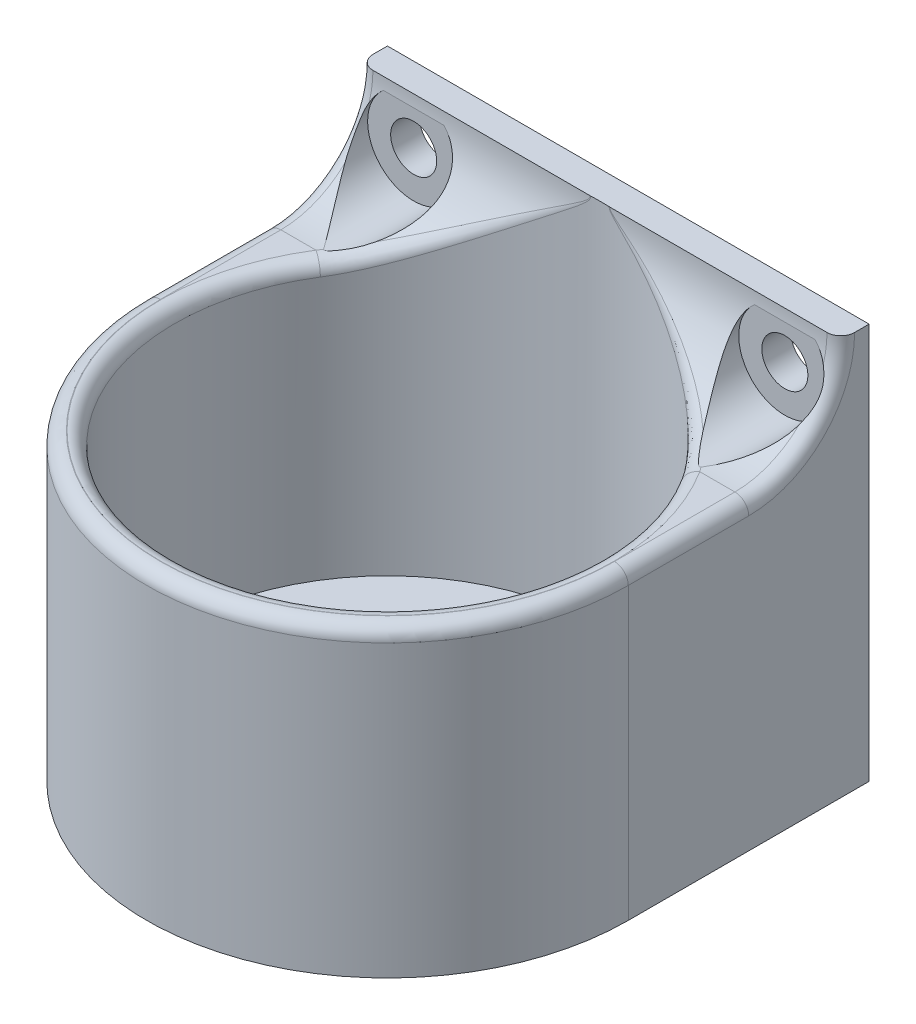
SolidWorks part; units mm, degrees
ref_plane "Front Plane" through (0, 0, 0) normal (0, 0, 1) x (1, 0, 0)
ref_plane "Top Plane" through (0, 0, 0) normal (0, 1, 0) x (1, 0, 0)
ref_plane "Right Plane" through (0, 0, 0) normal (1, 0, 0) x (0, 0, -1)
sketch "Sketch1" plane through (0, 0, 0) normal (0, 1, 0) x (1, 0, 0)
  circle A0 centre (0, 0) radius 26.15
  dimension "D1" = 52.3
extrude "Boss-Extrude1" add sketch "Sketch1" along normal blind 43
sketch "Sketch2" plane through (0, 43, 0) normal (0, 1, 0) x (1, 0, 0)
  line L0 (-26.15, 0) -> (-26.15, 26.15)
  line L1 (-26.15, 26.15) -> (0, 26.15)
  line L2 (0, 26.15) -> (26.15, 26.15)
  line L3 (26.15, 26.15) -> (26.15, 0)
  line L4 (26.15, 0) -> (-26.15, 0)
  circle A0 centre (0, 0) radius 26.15 construction
extrude "Boss-Extrude2" add sketch "Sketch2" against normal up to surface (43 mm away) up to face at (0, 0, 26.15)
sketch "Sketch3" plane through (0, 43, 0) normal (0, 1, 0) x (1, 0, 0)
  circle A0 centre (0, 0) radius 23.1
  dimension "D1" = 46.2
extrude "Cut-Extrude1" cut sketch "Sketch3" against normal offset from surface (40 mm away) 3 up to face at (0, 0, -6.5375)
sketch "Sketch5" plane through (0, 43, 0) normal (0, 1, 0) x (1, 0, 0)
  line L1 (-32.5077, 23.0771) -> (34.5641, 23.0771)
  line L2 (-32.5077, 23.0771) -> (-32.5077, -29.009)
  line L3 (-32.5077, -29.009) -> (34.5641, -29.009)
  line L4 (34.5641, 23.0771) -> (34.5641, -29.009)
  circle A0 centre (0, 0) radius 23.1 construction
  point P4 (1.0282, 23.0771)
extrude "Cut-Extrude3" cut sketch "Sketch5" against normal blind 10
sketch "Sketch6" plane through (0, 0, 0) normal (0, -1, 0) x (1, 0, 0)
  circle A0 centre (0, 0) radius 10
  dimension "D1" = 20
extrude "Cut-Extrude4" cut sketch "Sketch6" against normal up to surface (3 mm away) up to face at (0, 3, 23.1)
sketch "Sketch7" plane through (0, 0, -26.15) normal (0, 0, -1) x (-1, 0, 0)
  line L0 (-26.15, 0) -> (-26.15, 43) construction
  line L1 (26.15, 0) -> (26.15, 43) construction
  line L2 (-26.15, 43) -> (26.15, 43) construction
  circle A0 centre (-20.15, 38) radius 2.5
  circle A1 centre (20.15, 38) radius 2.5
  point P4 (0, 0)
  dimension "D1" = 5
  dimension "D2" = 5
  dimension "D3" = 6
  dimension "D4" = 6
  dimension "D5" = 5
extrude "Cut-Extrude5" cut sketch "Sketch7" against normal through all
fillet "Fillet5" radius 10 1 edges at (0, 3, 10)
fillet "Fillet7" radius 10 2 edges at (13.5891, 33, -23.0771) (-13.5891, 33, -23.0771)
fillet "Fillet8" radius 1.5 8 edges at (2.0521, 41.832, -23.0087) (-1.8332, 42.0016, -23.0271) (26.15, 35.9289, -20.1482) (26.15, 33, -6.5386) (0, 33, 26.15) (-26.15, 35.9289, -20.1482) (0, 33, 23.1) (-26.15, 33, -6.5386)
sketch "Sketch8" plane through (0, 0, 0) normal (0, 0, 1) x (1, 0, 0)
  circle A0 centre (-20.15, 38) radius 5
  circle A1 centre (20.15, 38) radius 5
  dimension "D1" = 10
  dimension "D2" = 10
extrude "Cut-Extrude10" cut sketch "Sketch8" against normal blind 23
